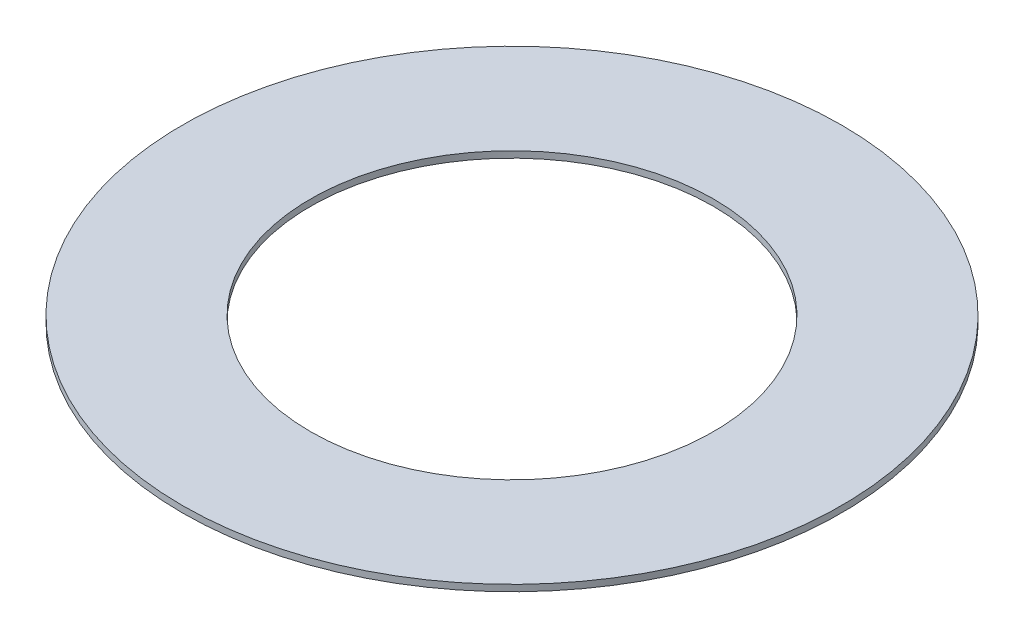
SolidWorks part; units mm, degrees
ref_plane "Front Plane" through (0, 0, 0) normal (0, 0, 1) x (1, 0, 0)
ref_plane "Top Plane" through (0, 0, 0) normal (0, 1, 0) x (1, 0, 0)
ref_plane "Right Plane" through (0, 0, 0) normal (1, 0, 0) x (0, 0, -1)
sketch "Sketch1" plane through (0, 0, 0) normal (0, 1, 0) x (1, 0, 0)
  circle A0 centre (0, 0) radius 130
  circle A1 centre (0, 0) radius 79.5
  circle A3 centre (0, 0) radius 87.5 construction
  dimension "D1" = 260
  dimension "D2" = 8
extrude "Boss-Extrude1" add sketch "Sketch1" along normal blind 2.54
